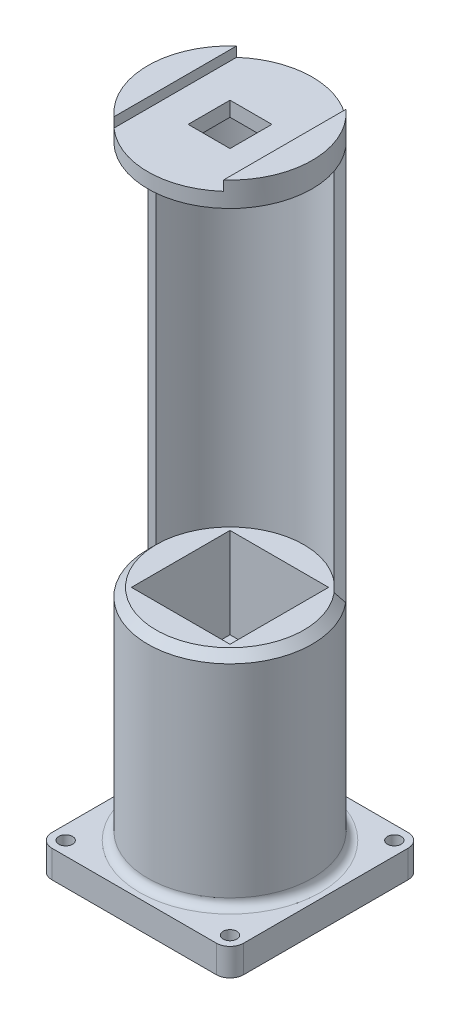
SolidWorks part; units mm, degrees
ref_plane "Front Plane" through (0, 0, 0) normal (0, 0, 1) x (1, 0, 0)
ref_plane "Top Plane" through (0, 0, 0) normal (0, 1, 0) x (1, 0, 0)
ref_plane "Right Plane" through (0, 0, 0) normal (1, 0, 0) x (0, 0, -1)
sketch "Sketch1" plane through (0, 0, 0) normal (0, 1, 0) x (1, 0, 0)
  line L1 (0, 0) -> (350, 0)
  line L2 (0, 0) -> (0, 350)
  line L3 (0, 350) -> (350, 350)
  line L4 (350, 0) -> (350, 350)
extrude "Boss-Extrude1" add sketch "Sketch1" against normal blind 50
fillet "Fillet1" radius 25 4 edges at (0, -25, -350) (350, -25, -350) (350, -25, 0) (0, -25, 0)
sketch "Sketch2" plane through (0, 0, 0) normal (0, 1, 0) x (1, 0, 0)
  circle A0 centre (25, 25) radius 12.5
  circle A1 centre (325, 25) radius 12.5
  circle A2 centre (325, 325) radius 12.5
  circle A3 centre (25, 325) radius 12.5
  dimension "D1" = 2
  dimension "D2" = 2
extrude "Cut-Extrude1" cut sketch "Sketch2" against normal blind 50
sketch "Sketch3" plane through (0, 0, 0) normal (0, 1, 0) x (1, 0, 0)
  circle A0 centre (175, 175) radius 150
extrude "Boss-Extrude2" add sketch "Sketch3" along normal blind 400
fillet "Fillet2" radius 15 1 edges at (175, 0, -325)
chamfer "Chamfer1" distance 15 angle 45 1 edges at (175, 400, -25)
sketch "Sketch5" plane through (0, 400, 0) normal (0, -1, 0) x (1, 0, 0)
  line L1 (265, -85) -> (85, -85)
  line L2 (265, -85) -> (265, -265)
  line L3 (265, -265) -> (85, -265)
  line L4 (85, -85) -> (85, -265)
  line L5 (265, -85) -> (85, -265) construction
  line L6 (265, -265) -> (85, -85) construction
  point P0 (175, -175)
extrude "Cut-Extrude3" cut sketch "Sketch5" along normal blind 165
scale "Scale1" scale about origin uniform scaling yes scale factor 0.333333
sketch "Sketch6" plane through (0, 133.3333, 0) normal (0, 1, 0) x (1, 0, 0)
  arc A0 (8.3333, 58.3333) -> (96.6356, 90.4727) centre (58.3333, 58.3333) cw
  circle A1 centre (58.3333, 58.3333) radius 50 construction
  circle A2 centre (58.3333, 58.3333) radius 50 construction
  point P8 (0, 0)
extrude "Extrude-Thin1" add sketch "Sketch6" against normal blind 5 and the other way blind 250 thin thin type one direction wall 5
sketch "Sketch7" plane through (0, 383.3333, 0) normal (0, 1, 0) x (1, 0, 0)
  circle A0 centre (58.3333, 58.3333) radius 50
extrude "Boss-Extrude3" add sketch "Sketch7" against normal blind 15 contours A0
sketch "Sketch8" plane through (0, 368.3333, 0) normal (0, -1, 0) x (1, 0, 0)
  line L1 (45.5833, -71.0833) -> (71.0833, -71.0833)
  line L2 (45.5833, -71.0833) -> (45.5833, -45.5833)
  line L3 (45.5833, -45.5833) -> (71.0833, -45.5833)
  line L4 (71.0833, -71.0833) -> (71.0833, -45.5833)
  line L5 (45.5833, -71.0833) -> (71.0833, -45.5833) construction
  line L6 (45.5833, -45.5833) -> (71.0833, -71.0833) construction
  point P0 (58.3333, -58.3333)
extrude "Cut-Extrude4" cut sketch "Sketch8" against normal blind 9.5
sketch "Sketch9" plane through (0, 383.3333, 0) normal (0, 1, 0) x (1, 0, 0)
  line L1 (91.6667, 108.3333) -> (25, 108.3333)
  line L2 (91.6667, 108.3333) -> (91.6667, 8.3333)
  line L3 (91.6667, 8.3333) -> (25, 8.3333)
  line L4 (25, 108.3333) -> (25, 8.3333)
  line L5 (91.6667, 108.3333) -> (25, 8.3333) construction
  line L6 (91.6667, 8.3333) -> (25, 108.3333) construction
  circle A0 centre (58.3333, 58.3333) radius 50 construction
  point P0 (58.3333, 58.3333)
extrude "Cut-Extrude5" cut sketch "Sketch9" against normal blind 6
